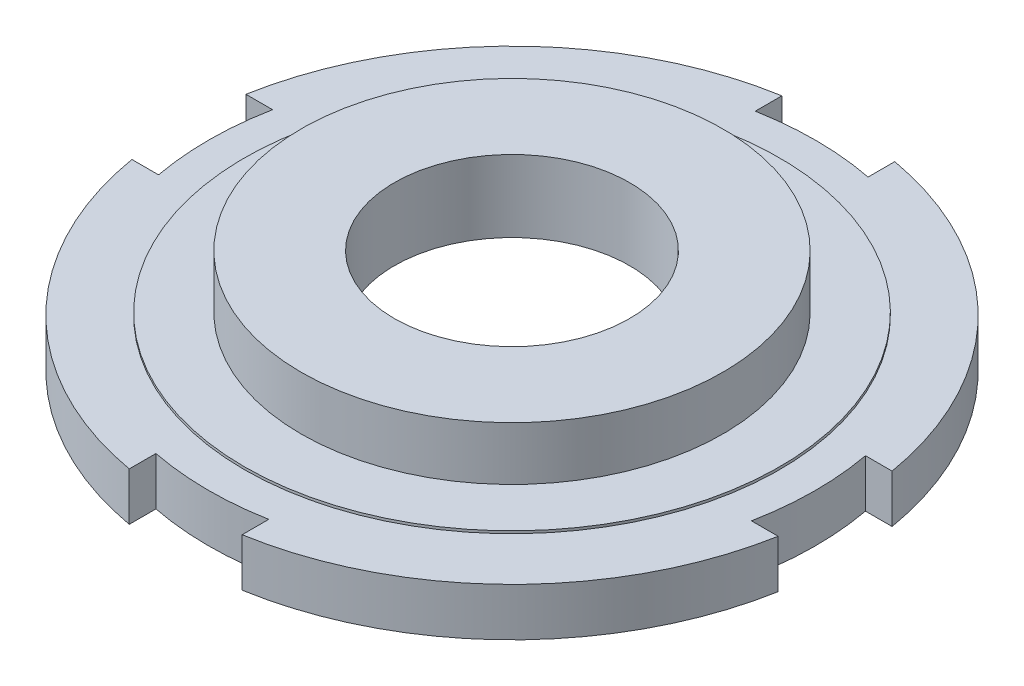
SolidWorks part; units mm, degrees
ref_plane "Front Plane" through (0, 0, 0) normal (0, 0, 1) x (1, 0, 0)
ref_plane "Top Plane" through (0, 0, 0) normal (0, 1, 0) x (1, 0, 0)
ref_plane "Right Plane" through (0, 0, 0) normal (1, 0, 0) x (0, 0, -1)
sketch "Sketch1" plane through (0, 0, 0) normal (0, 1, 0) x (1, 0, 0)
  line L0 (35.4054, 6.5405) -> (38.5653, 6.5405)
  line L1 (35.3329, -6.9215) -> (38.4988, -6.9215)
  line L2 (-55, 0) -> (55, 0) construction
  line L3 (6.5405, -35.4054) -> (6.5405, -38.5653)
  line L4 (-6.9215, -35.3329) -> (-6.9215, -38.4988)
  line L5 (-35.4054, -6.5405) -> (-38.5653, -6.5405)
  line L6 (-35.3329, 6.9215) -> (-38.4988, 6.9215)
  line L7 (-6.5405, 35.4054) -> (-6.5405, 38.5653)
  line L8 (6.9215, 35.3329) -> (6.9215, 38.4988)
  arc A1 (-38.5653, -6.5405) -> (-6.9215, -38.4988) centre (0, 0) ccw
  circle A2 centre (0, 0) radius 13.97
  arc A3 (-35.3329, 6.9215) -> (-35.4054, -6.5405) centre (0, 0) ccw
  arc A4 (6.9215, 35.3329) -> (-6.5405, 35.4054) centre (0, 0) ccw
  arc A5 (35.3329, -6.9215) -> (35.4054, 6.5405) centre (0, 0) ccw
  arc A6 (-6.9215, -35.3329) -> (6.5405, -35.4054) centre (0, 0) ccw
  arc A7 (6.5405, -38.5653) -> (38.4988, -6.9215) centre (0, 0) ccw
  arc A8 (38.5653, 6.5405) -> (6.9215, 38.4988) centre (0, 0) ccw
  arc A9 (-6.5405, 38.5653) -> (-38.4988, 6.9215) centre (0, 0) ccw
  point P26 (0, 0)
  dimension "D1" = 78.232
  dimension "D2" = 72.009
  dimension "D6" = 27.94
  dimension "D3" = 13.462
  dimension "D4" = 6.5405
  dimension "D5" = 4
ref_axis "Axis1" through (41.0751, 0, 0) along (-1, 0, 0)
ref_plane "Plane2" through (0, 0, 0) normal (0, -0.9903, 0.1392) x (-1, 0, 0)
ref_plane "Plane3" through (0, 6.2882, -0.8837) normal (0, -0.9903, 0.1392) x (-1, 0, 0)
extrude "Boss-Extrude2" add sketch "Sketch1" along normal blind 6
sketch "Sketch2" plane through (0, 0, 0) normal (0, -1, 0) x (1, 0, 0)
  line L3 (17.3777, -10.033) -> (-0.2866, -40.6283)
  line L4 (-4.5397, -40.3749) -> (8.1962, -18.3157)
  line L5 (3.2131, 0) -> (-3.2131, 0) construction
  arc A3 (8.1962, -18.3157) -> (17.3777, -10.033) centre (0, 0) cw
  arc A4 (-0.2866, -40.6283) -> (-4.5397, -40.3749) centre (0, 0) cw
  point P4 (8.5456, -25.3307)
  dimension "D1" = 20.066
  dimension "D2" = 3.81
  dimension "D3" = 60
extrude "Cut-Extrude1" cut sketch "Sketch2" against normal blind 3.81
sketch "Sketch3" plane through (0, 0, 0) normal (0, -1, 0) x (1, 0, 0)
  circle A0 centre (0, 0) radius 31.75
extrude "Cut-Extrude2" cut sketch "Sketch3" against normal blind 0.3
sketch "Sketch5" plane through (0, 6, 0) normal (0, 1, 0) x (1, 0, 0)
  circle A0 centre (0, 0) radius 25.019
  circle A1 centre (0, 0) radius 13.97 construction
  circle A2 centre (0, 0) radius 13.97
extrude "Boss-Extrude3" add sketch "Sketch5" along normal blind 6.35
sketch "Sketch6" plane through (0, 6, 0) normal (0, 1, 0) x (1, 0, 0)
  circle A0 centre (0, 0) radius 31.75
  circle A3 centre (0, 0) radius 50.8
  dimension "D1" = 63.5
  dimension "D2" = 101.6
extrude "Cut-Extrude3" cut sketch "Sketch6" against normal blind 0.3
